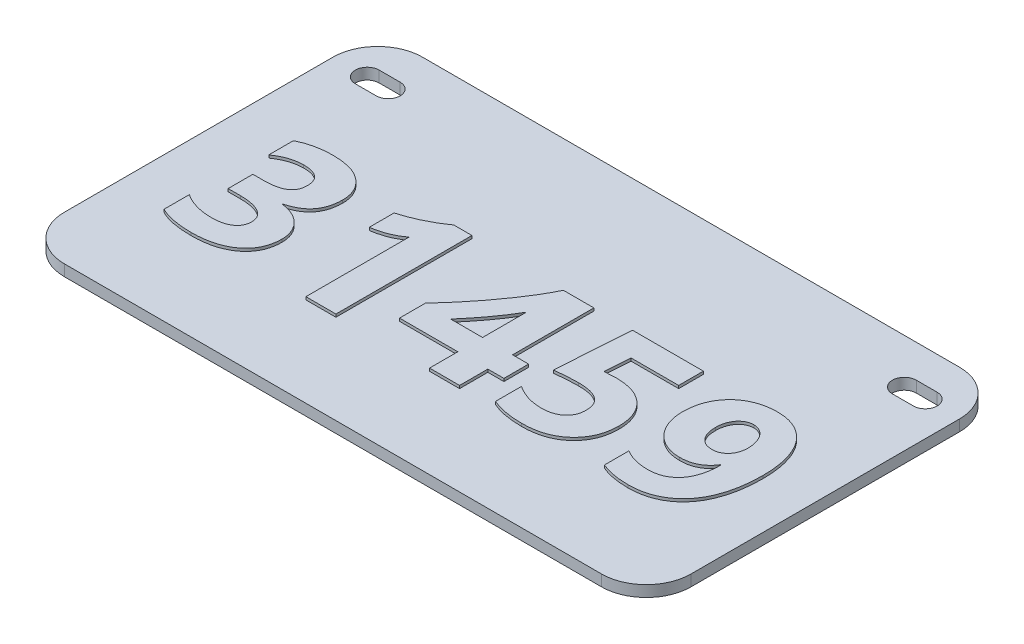
SolidWorks part; units mm, degrees
ref_plane "Front Plane" through (0, 0, 0) normal (0, 0, 1) x (1, 0, 0)
ref_plane "Top Plane" through (0, 0, 0) normal (0, 1, 0) x (1, 0, 0)
ref_plane "Right Plane" through (0, 0, 0) normal (1, 0, 0) x (0, 0, -1)
sketch "Sketch1" plane through (0, 0, 0) normal (0, 1, 0) x (1, 0, 0)
  line L1 (88.9, -50.8) -> (-88.9, -50.8)
  line L2 (88.9, -50.8) -> (88.9, 50.8)
  line L3 (88.9, 50.8) -> (-88.9, 50.8)
  line L4 (-88.9, -50.8) -> (-88.9, 50.8)
  line L5 (88.9, -50.8) -> (-88.9, 50.8) construction
  line L6 (88.9, 50.8) -> (-88.9, -50.8) construction
  point P0 (0, 0)
  dimension "D1" = 177.8
  dimension "D2" = 101.6
extrude "Boss-Extrude1" add sketch "Sketch1" along normal blind 3.175
hole_wizard "1/4 Clearance Slot1" positions "Sketch2" profile "Sketch3" size "1/4" standard "ANSI Inch" slot yes end condition through all
sketch "Sketch2" plane through (0, 3.175, 0) normal (0, 1, 0) x (1, 0, 0)
  line L0 (-82.55, 38.1) -> (-69.85, 38.1) construction
  line L1 (-88.9, 50.8) -> (-88.9, -50.8) construction
  line L2 (88.9, 50.8) -> (-88.9, 50.8) construction
  line L3 (88.9, -50.8) -> (88.9, 50.8) construction
  point P0 (-76.2, 38.1)
  point P4 (76.2, 38.1)
  dimension "D1" = 12.7
  dimension "D2" = 12.7
  dimension "D3" = 12.7
  dimension "D4" = 12.7
  dimension "D5" = 12.7
sketch "Sketch3" plane through (-76.2, 3.175, -38.1) normal (1, 0, 0) x (0, 0, 1)
  line L0 (0, 0) -> (0, 3.175)
  line L1 (0, 3.175) -> (3.3782, 3.175)
  line L2 (3.3782, 3.175) -> (3.3782, 0)
  line L5 (3.3782, 0) -> (0, 0)
  line L11 (0, -6.35) -> (0, 107.95) construction
  dimension "Thru Hole Dia." = 6.7564
  dimension "Thru Hole Depth" = 3.175
fillet "Fillet1" radius 12.7 4 edges at (88.9, 1.5875, 50.8) (-88.9, 1.5875, 50.8) (88.9, 1.5875, -50.8) (-88.9, 1.5875, -50.8)
sketch "Sketch5" plane through (0, 3.175, 0) normal (0, 1, 0) x (1, 0, 0)
  line L0 (-88.9, -25.4) -> (88.9, -25.4) construction
  line L1 (-88.9, 38.1) -> (-88.9, -38.1) construction
  line L2 (88.9, -38.1) -> (88.9, 38.1) construction
  text T0 "31459" font "Ebrima" height 38.1
  dimension "D1" = 25.4
extrude "Boss-Extrude2" add sketch "Sketch5" along normal blind 0.7937
equation "\"D3@Sketch2\"=\"D2@Sketch2\""
equation "\"D4@Sketch2\"=\"D2@Sketch2\""
equation "\"D5@Sketch2\"=\"D3@Sketch2\""
